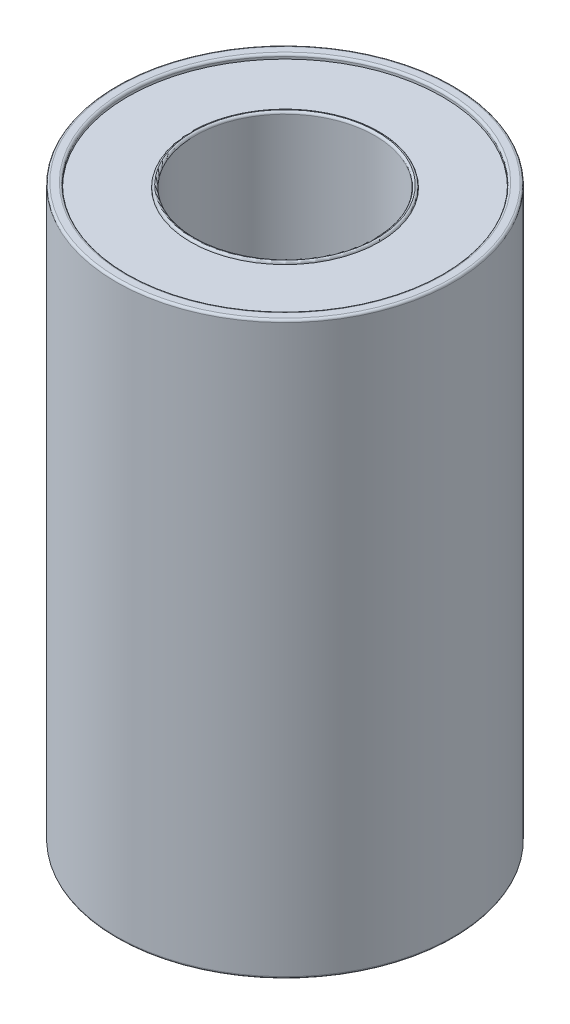
SolidWorks part; units mm, degrees
ref_plane "Front Plane" through (0, 0, 0) normal (0, 0, 1) x (1, 0, 0)
ref_plane "Top Plane" through (0, 0, 0) normal (0, 1, 0) x (1, 0, 0)
ref_plane "Right Plane" through (0, 0, 0) normal (1, 0, 0) x (0, 0, -1)
sketch "Sketch1" plane through (0, 0, 0) normal (0, 1, 0) x (1, 0, 0)
  circle A0 centre (0, 0) radius 7
extrude "Boss-Extrude1" add sketch "Sketch1" along normal mid plane 25
sketch "Sketch2" plane through (0, 12.5, 0) normal (0, 1, 0) x (1, 0, 0)
  circle A0 centre (0, 0) radius 4
extrude "Cut-Extrude1" cut sketch "Sketch2" against normal blind 25
sketch "Sketch3" plane through (0, 12.5, 0) normal (0, 1, 0) x (1, 0, 0)
  circle A0 centre (0, 0) radius 4 construction
  circle A1 centre (0, 0) radius 4
  circle A2 centre (0, 0) radius 4.2
  dimension "D1" = 0.2
extrude "Boss-Extrude2" add sketch "Sketch3" along normal blind 0.1
fillet "Fillet1" radius 0.1 2 edges at (0, 12.6, 4.2) (0, 12.6, 4)
mirror "Mirror1" about plane through (0, 0, 0) normal (0, 1, 0) of "Fillet1", "Boss-Extrude2"
sketch "Sketch4" plane through (0, 0, 0) normal (0, 1, 0) x (1, 0, 0)
  circle A0 centre (0, 0) radius 7.5
  circle A1 centre (0, 0) radius 7
  dimension "D1" = 0.5
extrude "Boss-Extrude4" add sketch "Sketch4" along normal mid plane 25.4
fillet "Fillet2" radius 0.1 2 edges at (0, 12.7, 7.5) (0, 12.7, 7)
fillet "Fillet3" radius 0.1 2 edges at (0, -12.7, 7) (0, -12.7, 7.5)
